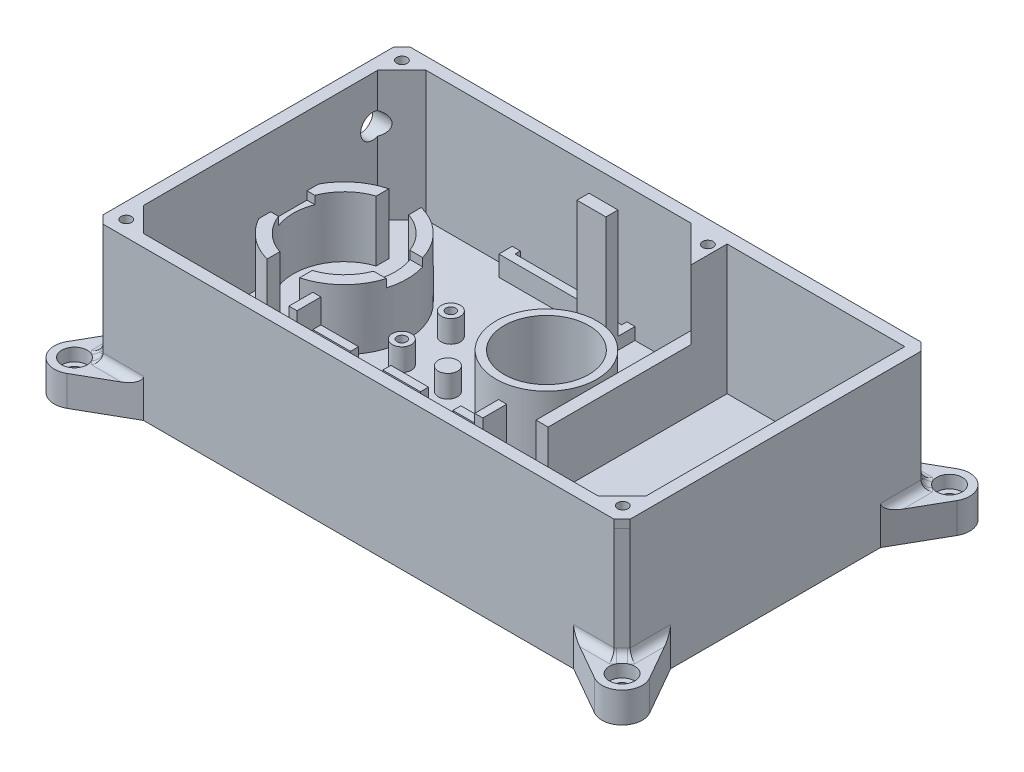
SolidWorks part; units mm, degrees
material "Nylon 101"
ref_plane "Front Plane" through (0, 0, 0) normal (0, 0, 1) x (1, 0, 0)
ref_plane "Top Plane" through (0, 0, 0) normal (0, 1, 0) x (1, 0, 0)
ref_plane "Right Plane" through (0, 0, 0) normal (1, 0, 0) x (0, 0, -1)
sketch "Sketch1" plane through (0, 0, 0) normal (0, 1, 0) x (1, 0, 0)
  line L1 (-125.4125, -114.3) -> (125.4125, -114.3)
  line L2 (-131.7625, -107.95) -> (-131.7625, 107.95)
  line L3 (-125.4125, 114.3) -> (125.4125, 114.3)
  line L4 (131.7625, -107.95) -> (131.7625, 107.95)
  line L5 (-131.7625, -114.3) -> (131.7625, 114.3) construction
  line L6 (-131.7625, 114.3) -> (131.7625, -114.3) construction
  line L7 (102.4819, -88.9) -> (-102.4819, -88.9)
  line L8 (102.4819, -88.9) -> (102.4819, 88.9)
  line L9 (102.4819, 88.9) -> (-102.4819, 88.9)
  line L10 (-102.4819, -88.9) -> (-102.4819, 88.9)
  line L11 (102.4819, -88.9) -> (-102.4819, 88.9) construction
  line L12 (102.4819, 88.9) -> (-102.4819, -88.9) construction
  arc A0 (-131.7625, 107.95) -> (-125.4125, 114.3) centre (-125.4125, 107.95) cw
  arc A1 (125.4125, 114.3) -> (131.7625, 107.95) centre (125.4125, 107.95) cw
  arc A2 (125.4125, -114.3) -> (131.7625, -107.95) centre (125.4125, -107.95) ccw
  arc A3 (-125.4125, -114.3) -> (-131.7625, -107.95) centre (-125.4125, -107.95) cw
  point P0 (0, 0)
  point P6 (0, 0)
  dimension "D4" = 6.35
  dimension "D1" = 263.525
  dimension "D2" = 228.6
  dimension "D3" = 25.4
extrude "Boss-Extrude1" add sketch "Sketch1" along normal blind 50.8
sketch "Sketch2" plane through (0, 0, 0) normal (0, -1, 0) x (-1, 0, 0)
  line L1 (-104.2522, 91.7587) -> (104.2522, 91.7587)
  line L2 (-104.2522, 91.7587) -> (-104.2522, -91.7587)
  line L3 (-104.2522, -91.7587) -> (104.2522, -91.7587)
  line L4 (104.2522, 91.7587) -> (104.2522, -91.7587)
  line L5 (-104.2522, 91.7587) -> (104.2522, -91.7587) construction
  line L6 (-104.2522, -91.7587) -> (104.2522, 91.7587) construction
  point P0 (0, 0)
extrude "Boss-Extrude2" add sketch "Sketch2" against normal blind 6.35
fillet "Fillet1" radius 6.35 4 edges at (102.4819, 28.575, -88.9) (-102.4819, 28.575, -88.9) (-102.4819, 28.575, 88.9) (102.4819, 28.575, 88.9)
sketch "Sketch3" plane through (0, 50.8, 0) normal (0, 1, 0) x (1, 0, 0)
  line L0 (125.4125, -86.2618) -> (103.7243, -107.95)
  line L1 (-125.4125, 107.95) -> (-103.7243, 107.95)
  line L2 (-125.4125, 107.95) -> (-125.4125, 86.2618)
  line L3 (-125.4125, -107.95) -> (-103.7243, -107.95)
  line L4 (125.4125, 107.95) -> (125.4125, 86.2618)
  line L5 (-125.4125, 107.95) -> (-113.7569, 97.9173) construction
  line L6 (-125.4125, -107.95) -> (-113.7569, -97.9173) construction
  line L7 (-96.1319, -88.9) -> (96.1319, -88.9) construction
  line L8 (-106.2919, 92.71) -> (106.2919, 92.71)
  line L9 (-106.2919, 92.71) -> (-106.2919, -92.71)
  line L10 (-106.2919, -92.71) -> (106.2919, -92.71)
  line L11 (106.2919, 92.71) -> (106.2919, -92.71)
  line L12 (-106.2919, 92.71) -> (106.2919, -92.71) construction
  line L13 (-103.7243, -107.95) -> (-125.4125, -86.2618)
  line L14 (125.4125, 86.2618) -> (103.7243, 107.95)
  line L15 (-106.2919, -92.71) -> (106.2919, 92.71) construction
  line L16 (125.4125, 86.2618) -> (125.4125, 107.95)
  line L17 (125.4125, 107.95) -> (103.7243, 107.95)
  line L18 (-103.7243, 107.95) -> (-125.4125, 86.2618)
  line L19 (103.7243, 107.95) -> (125.4125, 107.95)
  line L20 (-125.4125, -86.2618) -> (-125.4125, -107.95)
  line L21 (103.7243, -107.95) -> (125.4125, -107.95)
  line L22 (113.7569, -97.9173) -> (125.4125, -107.95) construction
  line L23 (125.4125, -86.2618) -> (125.4125, -107.95)
  line L24 (113.7569, 97.9173) -> (125.4125, 107.95) construction
  line L25 (102.4819, 82.55) -> (102.4819, -82.55) construction
  line L27 (125.4125, -86.2618) -> (125.4125, 86.2618)
  line L28 (103.7243, 107.95) -> (-103.7243, 107.95)
  line L29 (-125.4125, 86.2618) -> (-125.4125, -86.2618)
  line L30 (-103.7243, -107.95) -> (103.7243, -107.95)
  point P0 (0, 0)
  point P6 (0, 0)
  point P7 (0, 0)
  dimension "D1" = 3.81
  dimension "D2" = 3.81
extrude "Cut-Extrude1" cut sketch "Sketch3" against normal blind 44.45 contours L13 L30 L0 L27 L14 L28 L18 L29 L8 L11 L10 L9 region at (112.2282, 50.8, 94.7657)
fillet "Fillet2" radius 6.35 4 edges at (-106.2919, 28.575, -92.71) (-106.2919, 28.575, 92.71) (106.2919, 28.575, 92.71) (106.2919, 28.575, -92.71)
sketch "Sketch4" plane through (0, 50.8, 0) normal (0, 1, 0) x (1, 0, 0)
  line L1 (119.253, 111.379) -> (-119.253, 111.379)
  line L2 (128.905, 101.727) -> (128.905, -101.727)
  line L3 (119.253, -111.379) -> (-119.253, -111.379)
  line L4 (-128.905, 101.727) -> (-128.905, -101.727)
  line L5 (128.905, 111.379) -> (-128.905, -111.379) construction
  line L6 (128.905, -111.379) -> (-128.905, 111.379) construction
  arc A0 (-119.253, -111.379) -> (-128.905, -101.727) centre (-119.253, -101.727) cw
  arc A1 (-119.253, 111.379) -> (-128.905, 101.727) centre (-119.253, 101.727) ccw
  arc A2 (119.253, 111.379) -> (128.905, 101.727) centre (119.253, 101.727) cw
  arc A3 (128.905, -101.727) -> (119.253, -111.379) centre (119.253, -101.727) cw
  point P0 (0, 0)
  dimension "D3" = 9.652
  dimension "D1" = 222.758
  dimension "D2" = 257.81
extrude "Cut-Extrude2" cut sketch "Sketch4" against normal blind 5.08
sketch "Sketch5" plane through (0, 45.72, 0) normal (0, 1, 0) x (1, 0, 0)
  line L1 (128.5875, 111.125) -> (-128.5875, 111.125)
  line L2 (128.5875, 111.125) -> (128.5875, -111.125)
  line L3 (128.5875, -111.125) -> (-128.5875, -111.125)
  line L4 (-128.5875, 111.125) -> (-128.5875, -111.125)
  line L5 (128.5875, 111.125) -> (-128.5875, -111.125) construction
  line L6 (128.5875, -111.125) -> (-128.5875, 111.125) construction
  circle A0 centre (120.65, -103.1875) radius 4.318
  circle A1 centre (120.65, 103.1875) radius 4.318
  circle A2 centre (-120.65, 103.1875) radius 4.318
  circle A3 centre (-120.65, -103.1875) radius 4.318
  point P12 (0, 0)
  dimension "D1" = 222.25
  dimension "D3" = 7.9375
  dimension "D5" = 7.9375
  dimension "D6" = 7.9375
  dimension "D7" = 7.9375
  dimension "D8" = 7.9375
  dimension "D9" = 7.9375
  dimension "D10" = 7.9375
  dimension "D2" = 257.175
  dimension "D4" = 7.9375
extrude "Cut-Extrude3" cut sketch "Sketch5" against normal blind 7.9375 contours A3 | A2 | A1 | A0 region at (120.65, 45.72, 103.1875) region at (120.65, 45.72, -103.1875) region at (-120.65, 45.72, -103.1875) region at (-120.65, 45.72, 103.1875)
fillet "Fillet4" radius 1.27 8 edges at (-129.9026, 50.8, 112.4401) (-131.7625, 50.8, 0) (-129.9026, 50.8, -112.4401) (0, 50.8, -114.3) (129.9026, 50.8, -112.4401) (131.7625, 50.8, 0) (129.9026, 50.8, 112.4401) (0, 50.8, 114.3)
sketch "Sketch7" plane through (0, 45.72, 0) normal (0, 1, 0) x (1, 0, 0)
  line L1 (107.5535, 93.776) -> (-107.5535, 93.776)
  line L2 (107.5535, 93.776) -> (107.5535, -93.776)
  line L3 (107.5535, -93.776) -> (-107.5535, -93.776)
  line L4 (-107.5535, 93.776) -> (-107.5535, -93.776)
  line L5 (107.5535, 93.776) -> (-107.5535, -93.776) construction
  line L6 (107.5535, -93.776) -> (-107.5535, 93.776) construction
  point P0 (0, 0)
extrude "Cut-Extrude4" cut sketch "Sketch7" against normal up to surface (39.37 mm away) up to face at (0, 6.35, 0)
sketch "Sketch8" plane through (0, 6.35, 0) normal (0, 1, 0) x (1, 0, 0)
  circle A0 centre (0, 0) radius 13.335
  dimension "D1" = 26.67
extrude "Cut-Extrude5" cut sketch "Sketch8" against normal blind 0.254
sketch "Sketch9" plane through (0, 6.35, 0) normal (0, 1, 0) x (1, 0, 0)
  line L1 (77.1242, 35.56) -> (21.2442, 35.56)
  line L2 (77.1242, 35.56) -> (77.1242, -35.56)
  line L3 (77.1242, -35.56) -> (21.2442, -35.56)
  line L4 (21.2442, 35.56) -> (21.2442, -35.56)
  line L5 (77.1242, 35.56) -> (21.2442, -35.56) construction
  line L6 (77.1242, -35.56) -> (21.2442, 35.56) construction
  line L7 (80.9342, -39.37) -> (17.4342, -39.37)
  line L8 (80.9342, -39.37) -> (80.9342, 39.37)
  line L9 (80.9342, 39.37) -> (17.4342, 39.37)
  line L10 (17.4342, -39.37) -> (17.4342, 39.37)
  line L11 (80.9342, -39.37) -> (17.4342, 39.37) construction
  line L12 (80.9342, 39.37) -> (17.4342, -39.37) construction
  point P0 (49.1842, 0)
  point P5 (49.1842, 0)
  dimension "D1" = 55.88
  dimension "D2" = 71.12
  dimension "D3" = 3.81
  dimension "D4" = 3.81
extrude "Boss-Extrude3" add sketch "Sketch9" along normal blind 19.05
fillet "Fillet5" radius 1.27 8 edges at (49.1842, 6.35, 39.37) (80.9342, 6.35, 0) (17.4342, 6.35, 0) (49.1842, 6.35, -39.37) (80.9342, 15.875, -39.37) (17.4342, 15.875, -39.37) (80.9342, 15.875, 39.37) (17.4342, 15.875, 39.37)
sketch "Sketch10" plane through (0, 6.35, 0) normal (0, 1, 0) x (1, 0, 0)
  line L0 (18.7042, 40.64) -> (79.6642, 40.64) construction
  line L1 (-84.836, 57.15) -> (80.9342, 57.15)
  line L2 (-84.836, 57.15) -> (-84.836, -57.15)
  line L3 (-84.836, -57.15) -> (80.9342, -57.15)
  line L4 (80.9342, 57.15) -> (80.9342, -57.15)
  line L5 (79.6642, -40.64) -> (18.7042, -40.64) construction
  line L7 (-81.026, 53.34) -> (77.1242, 53.34)
  line L8 (-81.026, 53.34) -> (-81.026, -53.34)
  line L9 (-81.026, -53.34) -> (77.1242, -53.34)
  line L10 (77.1242, 53.34) -> (77.1242, -53.34)
  line L11 (80.9342, -38.1) -> (80.9342, 38.1) construction
  point P0 (0, 0)
  point P6 (0, 0)
  dimension "D1" = 3.81
  dimension "D2" = 3.81
  dimension "D3" = 3.81
  dimension "D4" = 3.81
  dimension "D5" = 12.7
  dimension "D6" = 12.7
  dimension "D7" = 0
  dimension "D8" = 81.026
extrude "Boss-Extrude4" add sketch "Sketch10" along normal blind 19.05
sketch "Sketch11" plane through (0, 25.4, 0) normal (0, 1, 0) x (1, 0, 0)
  line L0 (77.1242, 35.56) -> (21.2442, 35.56) construction
  line L2 (32.2926, 35.56) -> (32.2926, 40.64)
  line L3 (32.2926, 40.64) -> (21.2442, 40.64)
  line L4 (21.2442, 35.56) -> (21.2442, 40.64)
  line L5 (18.7042, 40.64) -> (77.1242, 40.64) construction
  line L6 (77.1242, -40.64) -> (18.7042, -40.64) construction
  line L8 (32.2926, 35.56) -> (32.2926, -40.64)
  line L9 (32.2926, -40.64) -> (21.2442, -40.64)
  line L10 (21.2442, 35.56) -> (21.2442, -40.64)
extrude "Cut-Extrude7" cut sketch "Sketch11" against normal blind 15.24
chamfer "Chamfer1" distance 5.08 angle 45 8 edges at (-131.7625, 0, 0) (-129.9026, 0, 112.4401) (0, 0, 114.3) (129.9026, 0, 112.4401) (131.7625, 0, 0) (129.9026, 0, -112.4401) (0, 0, -114.3) (-129.9026, 0, -112.4401)
sketch "Sketch15" plane through (-131.7625, 0, 0) normal (-1, 0, 0) x (0, 0, 1)
  text T0 "SMART-VIBES" font "Century Gothic" height in points 36
extrude "Cut-Extrude9" cut sketch "Sketch15" against normal blind 2.54
sketch "Sketch16" plane through (0, 6.35, 0) normal (0, 1, 0) x (1, 0, 0)
  circle A0 centre (0, 0) radius 13.335
  circle A1 centre (0, 0) radius 15.875
  dimension "D1" = 2.54
  dimension "D2" = 26.67
extrude "Boss-Extrude5" add sketch "Sketch16" along normal up to surface (19.05 mm away) up to face at (35.822, 25.4, 0)
sketch "Sketch17" plane through (0, 6.35, 0) normal (0, 1, 0) x (1, 0, 0)
  line L1 (-43.7959, 11.684) -> (-18.3959, 11.684)
  line L2 (-43.7959, 11.684) -> (-43.7959, -11.684)
  line L3 (-43.7959, -11.684) -> (-18.3959, -11.684)
  line L4 (-18.3959, 11.684) -> (-18.3959, -11.684)
  line L5 (-43.7959, 11.684) -> (-18.3959, -11.684) construction
  line L6 (-43.7959, -11.684) -> (-18.3959, 11.684) construction
  point P0 (-31.0959, 0)
  dimension "D1" = 25.4
  dimension "D2" = 23.368
extrude "Cut-Extrude10" cut sketch "Sketch17" against normal blind 2.54
sketch "Sketch18" plane through (0, 25.4, 0) normal (0, 1, 0) x (1, 0, 0)
  line L0 (77.1242, -35.56) -> (77.1242, 35.56) construction
  line L1 (77.1242, 27.94) -> (82.2042, 27.94)
  line L2 (77.1242, 27.94) -> (77.1242, -27.94)
  line L3 (77.1242, -27.94) -> (82.2042, -27.94)
  line L4 (82.2042, 27.94) -> (82.2042, -27.94)
  line L5 (82.2042, 38.1) -> (82.2042, -38.1) construction
  line L6 (21.2442, -35.56) -> (77.1242, -35.56) construction
  line L7 (77.1242, 35.56) -> (32.2926, 35.56) construction
  dimension "D1" = 7.62
  dimension "D2" = 7.62
extrude "Cut-Extrude11" cut sketch "Sketch18" against normal up to surface (19.05 mm away) up to face at (0, 6.35, 0)
sketch "Sketch19" plane through (0, 6.35, 0) normal (0, 1, 0) x (1, 0, 0)
  line L0 (-43.7959, 11.684) -> (-43.7959, -11.684) construction
  circle A0 centre (-63.6079, 0) radius 16.002
  circle A1 centre (-63.6079, 0) radius 19.812
  point P3 (-43.7959, 0)
  point P6 (-43.7959, 0)
  dimension "D1" = 3.81
extrude "Boss-Extrude6" add sketch "Sketch19" along normal up to surface (19.05 mm away) up to face at (36.9089, 25.4, 0)
sketch "Sketch20" plane through (0, 25.4, 0) normal (0, 1, 0) x (1, 0, 0)
  line L1 (-68.709, 23.2075) -> (-58.5069, 23.2075)
  line L2 (-68.709, 23.2075) -> (-68.709, -23.2075)
  line L3 (-68.709, -23.2075) -> (-58.5069, -23.2075)
  line L4 (-58.5069, 23.2075) -> (-58.5069, -23.2075)
  line L5 (-68.709, 23.2075) -> (-58.5069, -23.2075) construction
  line L6 (-68.709, -23.2075) -> (-58.5069, 23.2075) construction
  point P0 (-63.6079, 0)
extrude "Cut-Extrude12" cut sketch "Sketch20" against normal up to surface (19.05 mm away) up to face at (-8.4196, 6.35, 0)
sketch "Sketch21" plane through (0, 25.4, 0) normal (0, 1, 0) x (1, 0, 0)
  line L1 (-83.4199, -5.715) -> (-43.7959, -5.715)
  line L2 (-83.4199, -5.715) -> (-83.4199, 5.715)
  line L3 (-83.4199, 5.715) -> (-43.7959, 5.715)
  line L4 (-43.7959, -5.715) -> (-43.7959, 5.715)
  line L5 (-83.4199, -5.715) -> (-43.7959, 5.715) construction
  line L6 (-83.4199, 5.715) -> (-43.7959, -5.715) construction
  arc A0 (-58.5069, -19.1441) -> (-58.5069, 19.1441) centre (-63.6079, 0) ccw construction
  point P0 (-63.6079, 0)
  point P6 (-43.7959, 0)
  dimension "D1" = 11.43
extrude "Cut-Extrude13" cut sketch "Sketch21" against normal blind 2.54
sketch "Sketch23" plane through (0, 6.35, 0) normal (0, 1, 0) x (1, 0, 0)
  line L1 (77.1242, 27.94) -> (80.9342, 27.94)
  line L2 (77.1242, 27.94) -> (77.1242, -27.94)
  line L3 (77.1242, -27.94) -> (80.9342, -27.94)
  line L4 (80.9342, 27.94) -> (80.9342, -27.94)
extrude "Boss-Extrude7" add sketch "Sketch23" along normal blind 3.81
sketch "Sketch24" plane through (0, 6.35, 0) normal (0, 1, 0) x (1, 0, 0)
  line L1 (80.9342, -57.15) -> (-84.836, -57.15)
  line L2 (80.9342, -57.15) -> (80.9342, 57.15)
  line L3 (80.9342, 57.15) -> (-84.836, 57.15)
  line L4 (-84.836, -57.15) -> (-84.836, 57.15)
  line L5 (-131.7625, 114.3) -> (131.7625, 114.3)
  line L6 (-131.7625, 114.3) -> (-131.7625, -114.3)
  line L7 (-131.7625, -114.3) -> (131.7625, -114.3)
  line L8 (131.7625, 114.3) -> (131.7625, -114.3)
extrude "Cut-Extrude14" cut sketch "Sketch24" along normal through all and the other way through all
sketch "Sketch25" plane through (0, 10.16, 0) normal (0, 1, 0) x (1, 0, 0)
  line L1 (80.9342, -27.94) -> (77.1242, -27.94)
  line L2 (80.9342, -27.94) -> (80.9342, 27.94)
  line L3 (80.9342, 27.94) -> (77.1242, 27.94)
  line L4 (77.1242, -27.94) -> (77.1242, 27.94)
extrude "Boss-Extrude8" add sketch "Sketch25" along normal up to surface (15.24 mm away) up to face at (-0.8926, 25.4, 0)
sketch "Sketch26" plane through (0, 25.4, 0) normal (0, 1, 0) x (1, 0, 0)
  line L0 (32.2926, -39.37) -> (32.2926, -35.56) construction
  line L1 (72.9326, -43.1067) -> (62.7726, -43.1067)
  line L2 (72.9326, -43.1067) -> (72.9326, 43.4402)
  line L3 (72.9326, 43.4402) -> (62.7726, 43.4402)
  line L4 (62.7726, -43.1067) -> (62.7726, 43.4402)
  line L5 (52.6126, -43.1067) -> (42.4526, -43.1067)
  line L6 (52.6126, -43.1067) -> (52.6126, 43.4402)
  line L7 (52.6126, 43.4402) -> (42.4526, 43.4402)
  line L8 (42.4526, -43.1067) -> (42.4526, 43.4402)
  dimension "D1" = 10.16
  dimension "D2" = 10.16
  dimension "D3" = 10.16
  dimension "D4" = 10.16
extrude "Cut-Extrude15" cut sketch "Sketch26" against normal up to surface (19.05 mm away) up to face at (-14.6663, 6.35, 0)
fillet "Fillet6" radius 2.54 8 edges at (62.7726, 6.35, -38.1) (42.4526, 6.35, -38.1) (52.6126, 6.35, -38.1) (72.9326, 6.35, -38.1) (42.4526, 6.35, 38.1) (62.7726, 6.35, 38.1) (72.9326, 6.35, 38.1) (52.6126, 6.35, 38.1)
sketch "Sketch27" plane through (0, 25.4, 0) normal (0, 1, 0) x (1, 0, 0)
  line L0 (-80.9873, -5.715) -> (-83.4199, -5.715)
  line L1 (77.1242, -53.34) -> (-81.026, -53.34)
  line L2 (77.1242, -53.34) -> (77.1242, 53.34)
  line L3 (77.1242, 53.34) -> (-81.026, 53.34)
  line L4 (-81.026, -53.34) -> (-81.026, -5.715)
  line L5 (-84.836, 57.15) -> (80.9342, 57.15)
  line L6 (-84.836, 57.15) -> (-84.836, -57.15)
  line L7 (-84.836, -57.15) -> (80.9342, -57.15)
  line L8 (80.9342, 57.15) -> (80.9342, -57.15)
  line L10 (-83.4199, -5.715) -> (-78.5546, -5.715) construction
  line L11 (-83.4199, -5.715) -> (-83.4199, 5.715)
  line L12 (-83.4199, 5.715) -> (-80.9873, 5.715)
  line L13 (-78.5546, 5.715) -> (-83.4199, 5.715) construction
  line L14 (-81.026, 5.715) -> (-81.026, 53.34)
  line M3 (77.1242, -39.37) -> (77.1242, -53.34)
  line M4 (77.1242, -53.34) -> (-81.026, -53.34)
  line M5 (-81.026, -53.34) -> (-81.026, -9.4407)
  line M10 (-83.4199, -5.715) -> (-83.4199, 5.715)
  line M11 (-83.4199, 5.715) -> (-78.5546, 5.715)
  line M15 (-81.026, 9.4407) -> (-81.026, 53.34)
  line M16 (-81.026, 53.34) -> (77.1242, 53.34)
  line M17 (77.1242, 53.34) -> (77.1242, 39.37)
  line M21 (77.1242, 35.56) -> (77.1242, -35.56)
  line M23 (80.9342, -57.15) -> (80.9342, 57.15)
  line M24 (80.9342, 57.15) -> (-84.836, 57.15)
  line M25 (-84.836, 57.15) -> (-84.836, -57.15)
  line M26 (-84.836, -57.15) -> (80.9342, -57.15)
extrude "Boss-Extrude9" add sketch "Sketch27" along normal blind 19.177 contours L14 L2 L4 L0 M26 M23 M24 M25 M11 M15 M16 M17 M21 M3 M4 M5 M10 region at (-1.9509, 25.4, -55.1364)
sketch "Sketch28" plane through (0, 6.35, 0) normal (0, 1, 0) x (1, 0, 0)
  line L0 (-81.026, 5.715) -> (-81.026, 53.34) construction
  line L1 (77.1242, 35.56) -> (18.7042, 35.56)
  line L2 (77.1242, 35.56) -> (77.1242, 39.37)
  line L3 (77.1242, 39.37) -> (18.7042, 39.37)
  line L5 (18.7042, 39.37) -> (-81.026, 39.37)
  line L7 (18.7042, 35.56) -> (-81.026, 35.56)
  line L8 (-81.026, 39.37) -> (-81.026, 35.56)
extrude "Boss-Extrude10" add sketch "Sketch28" along normal up to surface (38.227 mm away) and the other way up to surface (6.35 mm away) up to face at (-1.9509, 44.577, 0) other way up to face at (-1.9509, 0, 0)
sketch "Sketch29" plane through (0, 6.35, 0) normal (0, 1, 0) x (1, 0, 0)
  line L0 (-84.836, 57.15) -> (-84.836, -57.15) construction
  line L1 (80.9342, 57.15) -> (-84.836, 57.15)
  line L2 (80.9342, 57.15) -> (80.9342, 39.37)
  line L3 (80.9342, 39.37) -> (-84.836, 39.37)
  line L4 (-84.836, 57.15) -> (-84.836, 39.37)
extrude "Cut-Extrude16" cut sketch "Sketch29" against normal through all and the other way through all
chamfer "Chamfer2" distance 2.54 angle 45 4 edges at (-84.836, 0, 8.89) (-1.9509, 0, 57.15) (80.9342, 0, 8.89) (-1.9509, 0, -39.37)
chamfer "Chamfer3" distance 2.54 angle 45 4 edges at (-84.836, 23.5585, 57.15) (-84.836, 23.5585, -39.37) (80.9342, 23.5585, -39.37) (80.9342, 23.5585, 57.15)
sketch "Sketch31" plane through (0, 6.35, 0) normal (0, 1, 0) x (1, 0, 0)
  line L1 (32.2926, -20.7193) -> (14.3781, -20.7193)
  line L2 (32.2926, -20.7193) -> (32.2926, -42.6994)
  line L3 (32.2926, -42.6994) -> (14.3781, -42.6994)
  line L4 (14.3781, -20.7193) -> (14.3781, -42.6994)
extrude "Cut-Extrude19" cut sketch "Sketch31" along normal through all
sketch "Sketch32" plane through (0, 3.81, 0) normal (0, 1, 0) x (1, 0, 0)
  line L1 (-43.7959, 11.684) -> (-18.3959, 11.684)
  line L2 (-43.7959, 11.684) -> (-43.7959, -11.684)
  line L3 (-43.7959, -11.684) -> (-18.3959, -11.684)
  line L4 (-18.3959, 11.684) -> (-18.3959, -11.684)
extrude "Boss-Extrude11" add sketch "Sketch32" along normal up to surface (2.54 mm away) up to face at (38.6426, 6.35, 38.1)
sketch "Sketch33" plane through (0, 6.35, 0) normal (0, 1, 0) x (1, 0, 0)
  line L0 (-37.7799, 7.7038) -> (-37.7799, -7.7038)
  circle A0 centre (-37.7799, 7.7038) radius 3
  circle A1 centre (-37.7799, -7.7038) radius 3
  circle A2 centre (-23.2892, 7.7038) radius 3
  circle A3 centre (-23.2892, -7.7038) radius 3
  point P4 (-37.7799, 0)
  dimension "D2" = 6
  dimension "D3" = 6
  dimension "D1" = 15.4076
extrude "Boss-Extrude12" add sketch "Sketch33" along normal blind 7 contours A1 | A0 | A2 | A3 region at (-35.7186, 6.35, 5.6425) region at (-39.8412, 6.35, -9.7651) region at (-23.2892, 6.35, -7.7038) region at (-23.2892, 6.35, 7.7038)
sketch "Sketch35" plane through (0, 13.35, 0) normal (0, 1, 0) x (1, 0, 0)
  circle A0 centre (-37.7799, 7.7038) radius 1.5
  circle A1 centre (-37.7799, -7.7038) radius 1.5
extrude "Cut-Extrude21" cut sketch "Sketch35" against normal blind 7
sketch "Sketch36" plane through (0, 6.35, 0) normal (0, 1, 0) x (1, 0, 0)
  line L1 (-49.9309, -23.5542) -> (5.9491, -23.5542)
  line L2 (-49.9309, -23.5542) -> (-49.9309, -47.6842)
  line L3 (-49.9309, -47.6842) -> (5.9491, -47.6842)
  line L4 (5.9491, -23.5542) -> (5.9491, -47.6842)
  line L5 (-52.4709, -21.0142) -> (8.4891, -21.0142)
  line L6 (-52.4709, -21.0142) -> (-52.4709, -50.2242)
  line L7 (-52.4709, -50.2242) -> (8.4891, -50.2242)
  line L8 (8.4891, -21.0142) -> (8.4891, -50.2242)
  dimension "D1" = 24.13
  dimension "D2" = 55.88
  dimension "D3" = 2.54
  dimension "D4" = 2.54
  dimension "D5" = 2.54
  dimension "D6" = 2.54
extrude "Boss-Extrude13" add sketch "Sketch36" along normal up to surface (19.05 mm away) up to face at (-77.2954, 25.4, 10.6591)
sketch "Sketch37" plane through (0, 25.4, 0) normal (0, 1, 0) x (1, 0, 0)
  line L0 (8.4891, -21.0142) -> (-52.4709, -21.0142) construction
  line L1 (5.9491, -23.5542) -> (-49.9309, -23.5542)
  line L2 (5.9491, -23.5542) -> (5.9491, -21.0142)
  line L3 (5.9491, -21.0142) -> (-49.9309, -21.0142)
  line L4 (-49.9309, -23.5542) -> (-49.9309, -21.0142)
extrude "Cut-Extrude22" cut sketch "Sketch37" against normal blind 7.62
sketch "Sketch38" plane through (0, 25.4, 0) normal (0, 1, 0) x (1, 0, 0)
  line L0 (8.4891, -50.2242) -> (8.4891, -21.0142) construction
  line L1 (8.4891, -28.5253) -> (5.9491, -28.5253)
  line L2 (8.4891, -28.5253) -> (8.4891, -42.7131)
  line L3 (8.4891, -42.7131) -> (5.9491, -42.7131)
  line L4 (5.9491, -28.5253) -> (5.9491, -42.7131)
  line L5 (5.9491, -47.6842) -> (5.9491, -23.5542) construction
  line L6 (8.4891, -28.5253) -> (8.4891, -21.0142)
  line L9 (8.4891, -50.2242) -> (8.4891, -42.7131)
  line M6 (5.9491, -21.0142) -> (5.9491, -47.6842)
  line M12 (8.4891, -50.2242) -> (8.4891, -21.0142)
extrude "Cut-Extrude23" cut sketch "Sketch38" against normal up to surface (19.05 mm away) contours L3 L1 M12 M6 region at (7.2191, 25.4, 35.6192) up to face at (-23.2892, 6.35, 4.7038)
sketch "Sketch39" plane through (0, 25.4, 0) normal (0, 1, 0) x (1, 0, 0)
  line L0 (-52.4709, -21.0142) -> (-52.4709, -50.2242) construction
  line L1 (-52.4709, -42.7131) -> (-49.9309, -42.7131)
  line L2 (-52.4709, -42.7131) -> (-52.4709, -28.5253)
  line L3 (-52.4709, -28.5253) -> (-49.9309, -28.5253)
  line L4 (-49.9309, -42.7131) -> (-49.9309, -28.5253)
  line L5 (-49.9309, -21.0142) -> (-49.9309, -47.6842) construction
  line L6 (8.4891, -42.7131) -> (5.9491, -42.7131) construction
  line L7 (8.4891, -28.5253) -> (5.9491, -28.5253) construction
extrude "Cut-Extrude24" cut sketch "Sketch39" against normal up to surface (19.05 mm away) up to face at (-12.2542, 6.35, 35.6192)
sketch "Sketch40" plane through (0, 17.78, 0) normal (0, 1, 0) x (1, 0, 0)
  line L0 (5.9491, -23.5542) -> (-49.9309, -23.5542) construction
  line L1 (-5.9042, -23.5542) -> (-16.0642, -23.5542)
  line L2 (-5.9042, -23.5542) -> (-5.9042, -21.0142)
  line L3 (-5.9042, -21.0142) -> (-16.0642, -21.0142)
  line L4 (-16.0642, -23.5542) -> (-16.0642, -21.0142)
  line L5 (8.4891, -21.0142) -> (-52.4709, -21.0142) construction
  line L6 (5.9491, -23.5542) -> (-5.9042, -23.5542)
  line L7 (-27.9176, -23.5542) -> (-38.0776, -23.5542)
  line L8 (-27.9176, -23.5542) -> (-27.9176, -21.0142)
  line L9 (-27.9176, -21.0142) -> (-38.0776, -21.0142)
  line L10 (-38.0776, -23.5542) -> (-38.0776, -21.0142)
  line L12 (-27.9176, -23.5542) -> (-16.0642, -23.5542)
  line L13 (-38.0776, -23.5542) -> (-49.9309, -23.5542)
  line M8 (5.9491, -21.0142) -> (-49.9309, -21.0142)
  line M10 (-49.9309, -23.5542) -> (5.9491, -23.5542)
  dimension "D1" = 10.16
  dimension "D2" = 10.16
extrude "Cut-Extrude25" cut sketch "Sketch40" against normal up to surface (11.43 mm away) contours L4 L2 M10 M8 | L10 L8 M10 M8 region at (-10.9842, 17.78, 22.2842) region at (-32.9976, 17.78, 22.2842) up to face at (-21.9909, 6.35, 25.4048)
sketch "Sketch41" plane through (-84.836, 0, 0) normal (-1, 0, 0) x (0, 0, 1)
  circle A0 centre (-26.3942, 32.6405) radius 3.81
extrude "Cut-Extrude26" cut sketch "Sketch41" against normal blind 7.62
sketch "Sketch42" plane through (0, 6.35, 0) normal (0, 1, 0) x (1, 0, 0)
  line L0 (-81.026, 35.56) -> (77.1242, 35.56) construction
  line L1 (-43.7959, 33.909) -> (-10.2679, 33.909)
  line L2 (-43.7959, 33.909) -> (-43.7959, 35.56)
  line L3 (-43.7959, 35.56) -> (-10.2679, 35.56)
  line L4 (-10.2679, 33.909) -> (-10.2679, 35.56)
  line L6 (-7.7279, 31.369) -> (-46.3359, 31.369)
  line L7 (-7.7279, 31.369) -> (-7.7279, 35.56)
  line L8 (-7.7279, 35.56) -> (-46.3359, 35.56)
  line L9 (-46.3359, 31.369) -> (-46.3359, 35.56)
  dimension "D1" = 33.528
  dimension "D2" = 1.651
  dimension "D3" = 2.54
  dimension "D4" = 2.54
  dimension "D5" = 2.54
extrude "Boss-Extrude14" add sketch "Sketch42" along normal blind 6.35 contours L9 L6 L7 L8 L4 L1 L2 region at (-27.0319, 6.35, -32.8041)
sketch "Sketch43" plane through (0, 12.7, 0) normal (0, 1, 0) x (1, 0, 0)
  line L0 (-43.7959, 35.56) -> (-10.2679, 35.56) construction
  line L1 (-7.7279, 31.369) -> (-16.8533, 31.369)
  line L2 (-7.7279, 31.369) -> (-7.7279, 35.56)
  line L3 (-7.7279, 35.56) -> (-16.8533, 35.56)
  line L4 (-16.8533, 31.369) -> (-16.8533, 35.56)
extrude "Cut-Extrude27" cut sketch "Sketch43" against normal blind 2.54
sketch "Sketch44" plane through (0, 6.35, 0) normal (0, 1, 0) x (1, 0, 0)
  line L0 (-81.026, 35.56) -> (77.1242, 35.56) construction
  line L1 (-7.7279, 31.369) -> (-16.8533, 31.369)
  line L2 (-7.7279, 31.369) -> (-7.7279, 30.226)
  line L3 (-7.7279, 30.226) -> (-16.8533, 30.226)
  line L4 (-16.8533, 31.369) -> (-16.8533, 30.226)
  line L5 (-16.8533, 33.909) -> (-16.8533, 31.369) construction
  line L6 (-7.7279, 30.226) -> (-16.8533, 30.226)
  line L7 (-7.7279, 30.226) -> (-7.7279, 26.416)
  line L8 (-7.7279, 26.416) -> (-16.8533, 26.416)
  line L9 (-16.8533, 30.226) -> (-16.8533, 26.416)
  dimension "D1" = 5.334
  dimension "D2" = 3.81
extrude "Boss-Extrude15" add sketch "Sketch44" along normal up to surface (3.81 mm away) contours L1 L4 L3 L2 | L3 L9 L8 L7 region at (-12.2906, 6.35, -30.7975) region at (-12.2906, 6.35, -28.321) up to face at (-11.6164, 10.16, -33.6127)
sketch "Sketch45" plane through (0, 10.16, 0) normal (0, 1, 0) x (1, 0, 0)
  line L0 (-16.8533, 31.369) -> (-16.8533, 26.416) construction
  line L1 (-16.8533, 26.416) -> (-7.7279, 26.416)
  line L2 (-16.8533, 26.416) -> (-16.8533, 30.226)
  line L3 (-16.8533, 30.226) -> (-7.7279, 30.226)
  line L4 (-7.7279, 26.416) -> (-7.7279, 30.226)
  line L5 (-16.8533, 31.369) -> (-16.8533, 26.416) construction
  line L6 (-7.7279, 26.416) -> (-7.7279, 35.56) construction
  line L7 (-7.7279, 26.416) -> (-16.8533, 26.416) construction
  dimension "D1" = 3.81
extrude "Boss-Extrude16" add sketch "Sketch45" along normal up to surface (34.417 mm away) up to face at (-1.9509, 44.577, 8.89)
sketch "Sketch46" plane through (0, 44.577, 0) normal (0, 1, 0) x (1, 0, 0)
  line L1 (77.1242, -53.34) -> (-81.026, -53.34)
  line L2 (77.1242, -53.34) -> (77.1242, 35.56)
  line L3 (77.1242, 35.56) -> (-81.026, 35.56)
  line L4 (-81.026, -53.34) -> (-81.026, 35.56)
  line L5 (-84.836, 39.37) -> (80.9342, 39.37)
  line L6 (-84.836, 39.37) -> (-84.836, -57.15)
  line L7 (-84.836, -57.15) -> (80.9342, -57.15)
  line L8 (80.9342, 39.37) -> (80.9342, -57.15)
extrude "Boss-Extrude17" add sketch "Sketch46" along normal blind 2.54
sketch "Sketch47" plane through (0, 22.86, 0) normal (0, 1, 0) x (1, 0, 0)
  line L1 (-81.026, 5.715) -> (-83.4199, 5.715)
  line L2 (-81.026, 5.715) -> (-81.026, -5.715)
  line L3 (-81.026, -5.715) -> (-83.4199, -5.715)
  line L4 (-83.4199, 5.715) -> (-83.4199, -5.715)
  line L10 (-81.026, 35.56) -> (-81.026, -53.34) construction
extrude "Boss-Extrude19" add sketch "Sketch47" along normal up to vertex (21.717 mm away) up to point (-81.026, 44.577, 5.715)
chamfer "Chamfer4" distance 2.54 angle 45 4 edges at (80.9342, 45.847, -39.37) (80.9342, 45.847, 57.15) (-84.836, 45.847, -39.37) (-84.836, 45.847, 57.15)
sketch "Sketch48" plane through (0, 47.117, 0) normal (0, 1, 0) x (1, 0, 0)
  line L0 (-93.5718, -57.2237) -> (-84.836, -41.91)
  line L1 (-84.836, 36.83) -> (-84.836, -54.61) construction
  line L2 (-84.9097, -65.8858) -> (-69.596, -57.15)
  line L3 (-88.0561, -60.3701) -> (-83.566, -55.88)
  line L4 (-82.296, -57.15) -> (78.3942, -57.15) construction
  line L5 (-84.836, -54.61) -> (-82.296, -57.15) construction
  line L6 (-84.836, -54.61) -> (-84.836, -41.91)
  line L7 (-82.296, -57.15) -> (-69.596, -57.15)
  line L8 (-88.0561, 42.5901) -> (-83.566, 38.1)
  line L9 (-82.296, 39.37) -> (-84.836, 36.83) construction
  line L11 (-84.836, 24.13) -> (-93.5718, 39.4437)
  line L12 (-69.596, 39.37) -> (-84.9097, 48.1058)
  line L13 (78.3942, 39.37) -> (-82.296, 39.37) construction
  line L14 (-84.836, 24.13) -> (-84.836, 36.83)
  line L15 (-82.296, 39.37) -> (-69.596, 39.37)
  line L16 (84.1544, 42.5901) -> (79.6642, 38.1)
  line L17 (80.9342, 36.83) -> (78.3942, 39.37) construction
  line L18 (78.3942, 39.37) -> (65.6942, 39.37)
  line L19 (80.9342, 36.83) -> (80.9342, 24.13)
  line L20 (80.9342, -54.61) -> (80.9342, 36.83) construction
  line L21 (65.6942, 39.37) -> (81.0079, 48.1058)
  line L22 (80.9342, 24.13) -> (89.67, 39.4437)
  line L23 (80.9342, -54.61) -> (80.9342, -41.91)
  line L24 (78.3942, -57.15) -> (65.6942, -57.15)
  line L25 (84.1544, -60.3701) -> (79.6642, -55.88)
  line L26 (78.3942, -57.15) -> (80.9342, -54.61) construction
  line L27 (65.6942, -57.15) -> (81.0079, -65.8858)
  line L28 (80.9342, -41.91) -> (89.67, -57.2237)
  line L29 (-84.836, 24.13) -> (-84.836, -41.91)
  line L30 (-69.596, -57.15) -> (65.6942, -57.15)
  line L31 (80.9342, -41.91) -> (80.9342, 24.13)
  line L32 (65.6942, 39.37) -> (-69.596, 39.37)
  circle A0 centre (-88.0561, 42.5901) radius 6.35
  circle A1 centre (-88.0561, -60.3701) radius 6.35
  circle A2 centre (84.1544, 42.5901) radius 6.35
  circle A3 centre (84.1544, -60.3701) radius 6.35
  dimension "D5" = 12.7
  dimension "D10" = 12.7
  dimension "D12" = 12.7
  dimension "D16" = 12.7
  dimension "D19" = 90
  dimension "D2" = 6.35
  dimension "D3" = 6.35
  dimension "D4" = 6.35
  dimension "D6" = 12.7
  dimension "D7" = 90
  dimension "D8" = 90
  dimension "D9" = 12.7
  dimension "D11" = 90
  dimension "D13" = 12.7
  dimension "D14" = 17.6302
  dimension "D15" = 6.35
  dimension "D17" = 12.7
  dimension "D18" = 17.6302
sketch "Sketch49" plane through (0, 0, 0) normal (0, -1, 0) x (1, 0, 0)
  line L0 (-93.5718, -39.4437) -> (-84.836, -24.13)
  line L1 (-84.9097, -48.1058) -> (-69.596, -39.37)
  line L2 (-88.0561, -42.5901) -> (-83.566, -38.1)
  line L3 (-84.836, -36.83) -> (-84.836, -24.13)
  line L4 (-82.296, -39.37) -> (-69.596, -39.37)
  line L5 (-88.0561, 60.3701) -> (-83.566, 55.88)
  line L6 (-84.836, 41.91) -> (-93.5718, 57.2237)
  line L7 (-69.596, 57.15) -> (-84.9097, 65.8858)
  line L8 (-84.836, 41.91) -> (-84.836, 54.61)
  line L9 (-82.296, 57.15) -> (-69.596, 57.15)
  line L10 (84.1544, 60.3701) -> (79.6642, 55.88)
  line L11 (78.3942, 57.15) -> (65.6942, 57.15)
  line L12 (80.9342, 54.61) -> (80.9342, 41.91)
  line L13 (65.6942, 57.15) -> (81.0079, 65.8858)
  line L14 (80.9342, 41.91) -> (89.67, 57.2237)
  line L15 (80.9342, -36.83) -> (80.9342, -24.13)
  line L16 (78.3942, -39.37) -> (65.6942, -39.37)
  line L17 (84.1544, -42.5901) -> (79.6642, -38.1)
  line L18 (65.6942, -39.37) -> (81.0079, -48.1058)
  line L19 (80.9342, -24.13) -> (89.67, -39.4437)
  line L20 (-84.836, 41.91) -> (-84.836, -24.13)
  line L21 (-69.596, -39.37) -> (65.6942, -39.37)
  line L22 (80.9342, -24.13) -> (80.9342, 41.91)
  line L23 (65.6942, 57.15) -> (-69.596, 57.15)
  line L24 (-84.836, -24.13) -> (-84.836, 41.91) construction
  line L25 (-69.596, 57.15) -> (65.6942, 57.15) construction
  line L26 (65.6942, -39.37) -> (-69.596, -39.37) construction
  line L27 (80.9342, 41.91) -> (80.9342, -24.13) construction
  line L28 (80.9342, 54.61) -> (79.6642, 55.88) construction
  line L29 (-93.5718, 57.2237) -> (-84.836, 41.91) construction
  line L30 (-84.9097, 65.8858) -> (-69.596, 57.15) construction
  circle A0 centre (-88.0561, 60.3701) radius 6.35
  circle A1 centre (-88.0561, -42.5901) radius 6.35
  circle A2 centre (84.1544, 60.3701) radius 6.35
  circle A3 centre (84.1544, -42.5901) radius 6.35
  point P38 (-84.836, 8.89)
  point P41 (-1.9509, 57.15)
  point P44 (-1.9509, -39.37)
  point P48 (80.9342, 8.89)
  line M11 (78.3942, 54.61) -> (-82.296, 54.61)
  line M12 (-82.296, 54.61) -> (-82.296, -36.83)
  line M13 (-82.296, -36.83) -> (78.3942, -36.83)
  line M14 (78.3942, -36.83) -> (78.3942, 54.61)
  dimension "D1" = 12.7
  dimension "D4" = 12.7
  dimension "D5" = 12.7
  dimension "D8" = 12.7
  dimension "D2" = 12.7
  dimension "D3" = 12.7
  dimension "D6" = 12.7
  dimension "D7" = 17.6302
  dimension "D9" = 12.7
  dimension "D10" = 17.6302
  dimension "D11" = 6.35
  dimension "D12" = 12.7
  dimension "D13" = 6.35
  dimension "D14" = 90
extrude "Boss-Extrude20" add sketch "Sketch49" against normal blind 9.525 contours A3 L19 L22 L14 A2 L13 L23 L7 A0 L6 L20 L0 A1 L1 L21 L18 M11 M14 M13 M12 | A0 | A1 | A3 | A2 region at (-87.3294, 0, -32.8562) region at (-88.8774, 0, -36.4746) region at (-92.4193, 0, 64.7333) region at (78.0389, 0, -43.4114) region at (87.2534, 0, 65.7058)
hole_wizard "CBORE for M4 SHCS3" positions "Sketch56" profile "Sketch55" counterbore size "M4" standard "ANSI Metric"
sketch "Sketch56" plane through (0, 9.525, 0) normal (0, 1, 0) x (1, 0, 0)
  point P0 (84.1544, 42.5901)
  point P3 (84.1544, -60.3701)
  point P6 (-88.0561, -60.3701)
  point P9 (-88.0561, 42.5901)
sketch "Sketch55" plane through (84.1544, 9.525, -42.5901) normal (1, 0, 0) x (0, 0, 1)
  line L0 (0, 0) -> (0, 26.7519)
  line L1 (0, 26.7519) -> (2.25, 25.4)
  line L2 (2.25, 25.4) -> (2.25, 4)
  line L3 (2.25, 4) -> (4, 4)
  line L4 (4, 4) -> (4, 0)
  line L5 (4, 0) -> (0, 0)
  line L10 (0, 26.7519) -> (-2.25, 25.4) construction
  line L11 (0, -6.35) -> (0, 107.95) construction
  dimension "Hole Dia." = 4.5
  dimension "Hole Depth" = 25.4
  dimension "C'Bore Dia." = 8
  dimension "C'Bore Depth" = 4
  dimension "Drill Angle" = 118
chamfer "Chamfer5" distance 7.62 angle 45 3 edges at (-81.026, 26.7335, -35.56) (-81.026, 26.7335, 53.34) (77.1242, 26.7335, 53.34)
sketch "Sketch57" plane through (0, 6.35, 0) normal (0, 1, 0) x (1, 0, 0)
  line L0 (16.1642, -20.7193) -> (16.1642, 35.56) construction
  line L1 (16.1642, 17.8789) -> (17.4342, 17.8789)
  line L2 (16.1642, 17.8789) -> (16.1642, 35.56)
  line L3 (16.1642, 35.56) -> (17.4342, 35.56)
  line L4 (17.4342, 17.8789) -> (17.4342, 35.56)
extrude "Cut-Extrude28" cut sketch "Sketch57" along normal blind 9.525
chamfer "Chamfer6" distance 7.62 angle 45 1 edges at (17.4342, 15.875, -35.56)
sketch "Sketch58" plane through (0, 25.4, 0) normal (0, 1, 0) x (1, 0, 0)
  line L0 (21.2442, 35.56) -> (9.8142, 35.56)
  line L1 (9.8142, 35.56) -> (17.4342, 27.94)
  line L2 (17.4342, 27.94) -> (21.2442, 24.13)
  line L3 (21.2442, 35.56) -> (21.2442, -20.7193) construction
  line L4 (21.2442, 24.13) -> (21.2442, 35.56)
extrude "Boss-Extrude21" add sketch "Sketch58" along normal up to surface (21.717 mm away) up to face at (-1.9509, 47.117, 8.89)
hole_wizard "Tap Drill for M4x0.7 Tap1" positions "Sketch61" profile "Sketch59" hole size "M4x0.7" standard "ANSI Metric"
sketch "Sketch61" plane through (0, 47.117, 0) normal (0, 1, 0) x (1, 0, 0)
  line L0 (-73.406, -53.34) -> (-81.026, -45.72) construction
  line L1 (-81.026, 27.94) -> (-73.406, 35.56) construction
  line L2 (77.1242, -45.72) -> (69.5042, -53.34) construction
  line L3 (9.8142, 35.56) -> (21.2442, 24.13) construction
  point P0 (-79.9101, 34.4441)
  point P2 (-79.9101, -52.2241)
  point P4 (76.1179, -52.1145)
  point P6 (18.3509, 32.4115)
  dimension "D1" = 3.81
  dimension "D2" = 3.81
  dimension "D3" = 3.81
  dimension "D4" = 3.81
sketch "Sketch59" plane through (-79.9101, 47.117, -34.4441) normal (1, 0, 0) x (0, 0, 1)
  line L0 (0, 0) -> (0, 26.3914)
  line L1 (0, 26.3914) -> (1.65, 25.4)
  line L2 (1.65, 25.4) -> (1.65, 0)
  line L5 (1.65, 0) -> (0, 0)
  line L10 (0, 26.3914) -> (-1.65, 25.4) construction
  line L11 (0, -6.35) -> (0, 107.95) construction
  dimension "Hole Dia." = 3.3
  dimension "Hole Depth" = 25.4
  dimension "Drill Angle" = 118
fillet "Fillet7" radius 2.54 12 edges at (-75.946, 9.525, 57.15) (-83.566, 9.525, 55.88) (-84.836, 9.525, 48.26) (-84.836, 9.525, -30.48) (-83.566, 9.525, -38.1) (-75.946, 9.525, -39.37) (72.0442, 9.525, 57.15) (79.6642, 9.525, 55.88) (80.9342, 9.525, 48.26) (80.9342, 9.525, -30.48) (79.6642, 9.525, -38.1) (72.0442, 9.525, -39.37)
